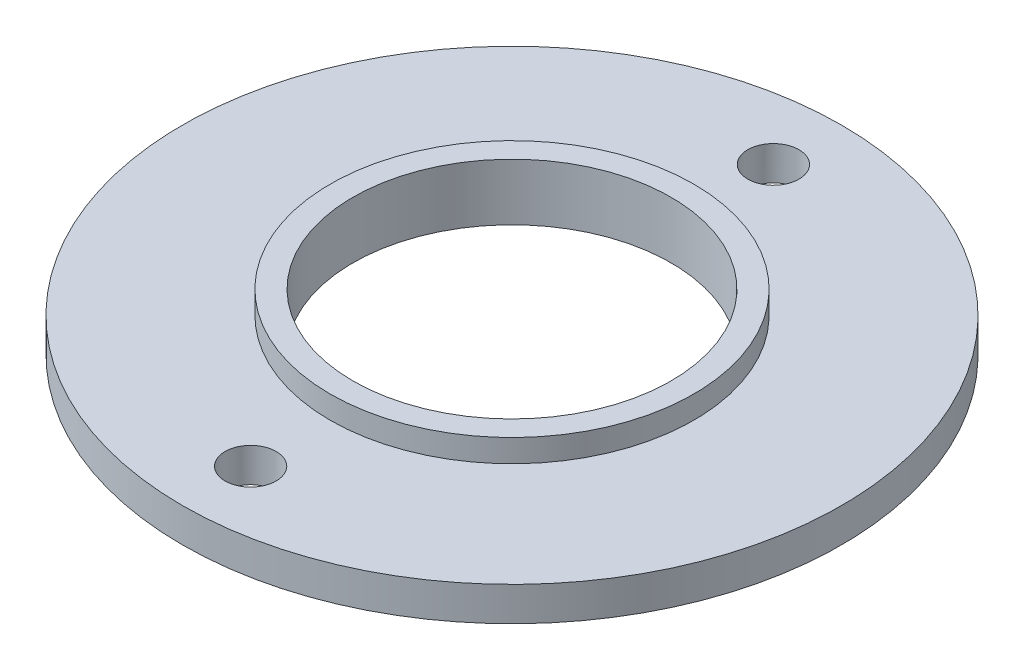
SolidWorks part; units mm, degrees
ref_plane "Front Plane" through (0, 0, 0) normal (0, 0, 1) x (1, 0, 0)
ref_plane "Top Plane" through (0, 0, 0) normal (0, 1, 0) x (1, 0, 0)
ref_plane "Right Plane" through (0, 0, 0) normal (1, 0, 0) x (0, 0, -1)
ref_axis "X" through (88.99, 0, 0) along (-1, 0, 0)
ref_axis "Y" through (0, 55, 0) along (0, -1, 0)
ref_axis "Z" through (0, 0, -88.99) along (0, 0, 1)
sketch "Sketch1" plane through (0, 0, 0) normal (0, 0, 1) x (1, 0, 0)
  line L0 (88.99, 0) -> (-88.99, 0) construction
  line L4 (-29, -1.5) -> (-29, 1.5)
  line L5 (-29, 1.5) -> (-16, 1.5)
  line L9 (-14, -1.5) -> (-29, -1.5)
  line L10 (-14, -1.5) -> (-14, 3.5)
  line L13 (-14, 3.5) -> (-16, 3.5)
  line L14 (-16, 1.5) -> (-16, 3.5)
  point P0 (-16, -6.4223)
  point P1 (0, 0)
  point P9 (-29, 0)
  dimension "D1" = 15
  dimension "D2" = 16
  dimension "D3" = 3
  dimension "D5" = 2
  dimension "D6" = 2
revolve "Revolve1" add sketch "Sketch1" angle 360 about axis through (0, 55, 0) along (0, -1, 0)
hole_wizard "M4 Clearance Hole1" positions "Sketch2" profile "Sketch3" hole size "M4" standard "DIN" end condition up to next
sketch "Sketch2" plane through (0, 1.5, 0) normal (0, 1, 0) x (1, 0, 0)
  circle A0 centre (0, 0) radius 23
  point P5 (0, 23)
  point P9 (0, -23)
  dimension "D1" = 46
sketch "Sketch3" plane through (0, 1.5, 23) normal (1, 0, 0) x (0, 0, 1)
  line L0 (0, 0) -> (0, 3)
  line L1 (0, 3) -> (2.25, 3)
  line L2 (2.25, 3) -> (2.25, 0)
  line L5 (2.25, 0) -> (0, 0)
  line L11 (0, -6.35) -> (0, 107.95) construction
  dimension "Thru Hole Dia." = 4.5
  dimension "Thru Hole Depth" = 3
